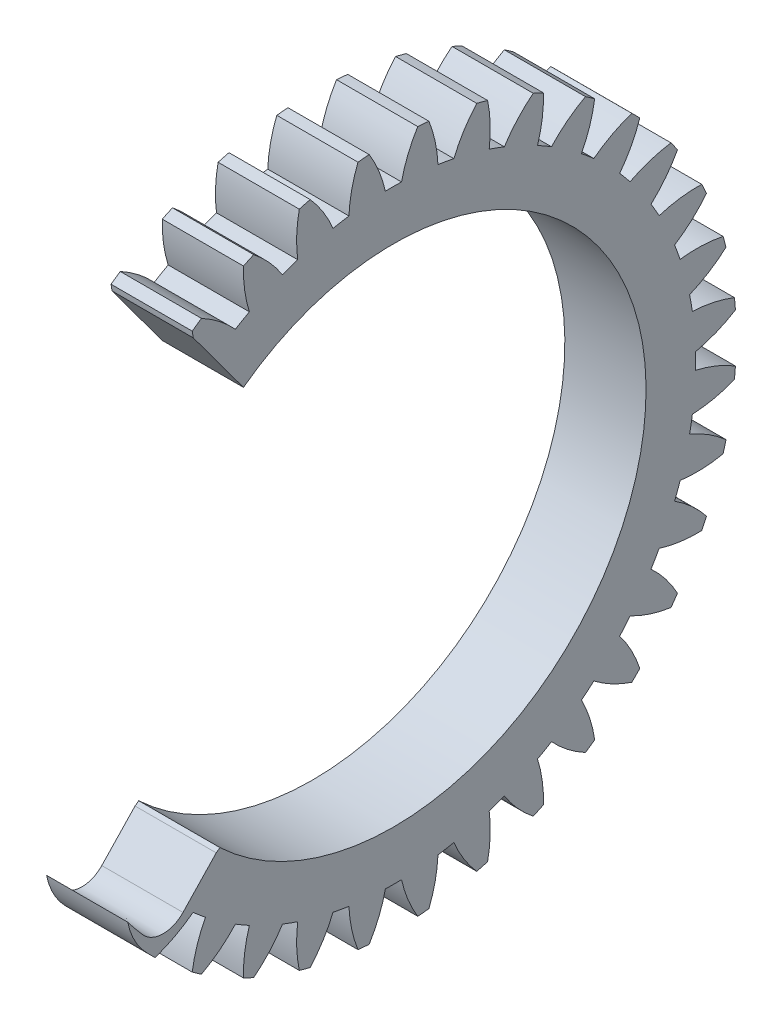
SolidWorks part; units mm, degrees
ref_plane "Plane1" through (0, 0, 0) normal (0, 0, 1) x (1, 0, 0)
ref_plane "Plane2" through (0, 0, 0) normal (0, 1, 0) x (1, 0, 0)
ref_plane "Plane3" through (0, 0, 0) normal (1, 0, 0) x (0, 0, -1)
sketch "HoldingSke" plane through (0, 0, 0) normal (0, 1, 0) x (1, 0, 0)
  line L0 (0, 0) -> (0.4045, -0.2939)
  line L1 (-15, 0) -> (100, 0) construction
  line L2 (0, 0) -> (-2.1039, 2.3779)
  line L3 (0, 0) -> (-11.863, 4.5341)
  line L4 (0, 0) -> (6.9867, 5.0761)
  line L5 (0, 0) -> (-46.8476, -17.4728)
  line L6 (0, 0) -> (-7.4607, -5.0337)
  line L7 (-2.1039, 2.3779) -> (8.6586, 51.2059)
  line L8 (-76.2, 54.61) -> (-71.9, 54.61)
  line L9 (-71.009, 38.7566) -> (-53.1078, 45.2721)
  line L10 (-76.2, 71.12) -> (104.1128, 71.12)
  line L11 (0, 0) -> (-9, 0)
  line L12 (-76.2, 101.6) -> (-76.133, 101.6)
  line L13 (24.9733, 27.94) -> (52.9518, 28.4284)
  line L14 (24.9733, 27.94) -> (24.9743, 27.94)
  line L15 (24.9733, 27.94) -> (100.4006, 29.5858)
  line L16 (-63.627, -2) -> (-12.827, -2)
  circle A0 centre (0, 0) radius 28
  circle A1 centre (0, 0) radius 33.499
  circle A2 centre (0, 0) radius 37.5
  circle A3 centre (0, 0) radius 28
  dimension "Num_teeth" = 36
  dimension "Pitch_radius" = 180.3128
  dimension "Width" = 9
  dimension "Thickness" = 9
sketch "BasProSke" plane through (0, 0, 0) normal (0, 1, 0) x (1, 0, 0)
  line L0 (-10, 0) -> (60, 0) construction
  line L1 (0, 0) -> (0, 38)
  line L2 (0, 0) -> (9, 0)
  line L3 (9, 0) -> (9, 38)
  line L4 (9, 38) -> (0, 38)
  dimension "Thickness" = 9
  dimension "Diameter" = 76
revolve "Base-Revolve" add sketch "BasProSke" angle 360 about L0
sketch "TooCutSke" plane through (0, 0, 0) normal (1, 0, 0) x (0, 0, -1)
  line L1 (0, 0) -> (0, 107) construction
  line L2 (0, 0) -> (-1.6875, 35.9604) construction
  line L3 (0, 0) -> (-6.2701, 71.6676) construction
  line L4 (-1.6875, 35.9604) -> (-3.135, 35.8338) construction
  arc A0 (0.8949, 33.487) -> (-0.8949, 33.487) centre (0, 0) ccw
  arc A1 (2.7061, 37.929) -> (-2.7061, 37.929) centre (0, 0) ccw
  circle A2 centre (0, 0) radius 36 construction
  circle A3 centre (0, 0) radius 33.8289 construction
  arc A4 (-0.8949, 33.487) -> (-2.7061, 37.929) centre (-14.9484, 30.347) ccw
  arc A5 (2.7061, 37.929) -> (0.8949, 33.487) centre (14.9484, 30.347) ccw
extrude "ToothCut" cut sketch "TooCutSke" along normal through all
fillet "Breaks" [suppressed] radius 0.04 tangent propagation no
fillet "RootFillets" [suppressed] radius 0.501
pattern_circular "TeethCuts" count 36 every 10 about axis through (-10, 0, 0) along (1, 0, 0) of "ToothCut", "RootFillets", "Breaks"
sketch "HubNeaOneSke" plane through (0, 0, 0) normal (-1, 0, 0) x (0, 0, 1)
  circle A0 centre (0, 0) radius 33.499
  dimension "Diameter" = 66.998
extrude "HubNearOne" [suppressed] add sketch "HubNeaOneSke" along normal blind 41.0001
sketch "HubNeaBotSke" plane through (0, 0, 0) normal (-1, 0, 0) x (0, 0, 1)
  circle A0 centre (0, 0) radius 33.499
  dimension "Diameter" = 66.998
extrude "HubNearBoth" [suppressed] add sketch "HubNeaBotSke" along normal blind 20.5
ref_plane "FarPln" through (9, 0, 0) normal (1, 0, 0) x (0, 0, -1)
sketch "HubFarSke" plane through (9, 0, 0) normal (1, 0, 0) x (0, 0, -1)
  circle A0 centre (0, 0) radius 33.499
  dimension "Diameter" = 66.998
extrude "HubFar" [suppressed] add sketch "HubFarSke" along normal blind 20.5
sketch "BorSke" plane through (0, 0, 0) normal (1, 0, 0) x (0, 0, -1)
  circle A0 centre (0, 0) radius 28
  dimension "Diameter" = 56
extrude "Bore" cut sketch "BorSke" along normal mid plane 100.0001
sketch "KeySke" plane through (0, 0, 0) normal (1, 0, 0) x (0, 0, -1)
  line L0 (-8, 0) -> (-8, 32.3)
  line L1 (-8, 32.3) -> (8, 32.3)
  line L2 (8, 32.3) -> (8, 0)
  line L3 (0, 0) -> (0, 34) construction
  line L4 (-8, 0) -> (8, 0)
  dimension "Width" = 16
extrude "Keyway" [suppressed] cut sketch "KeySke" along normal mid plane 100.0001
pattern_circular "Keyway2" [suppressed] count 2 every 90 about axis through (-10, 0, 0) along (1, 0, 0) reverse direction yes
sketch "Szkic1" plane through (0, 0, 0) normal (1, 0, 0) x (0, 0, -1)
  line L0 (0, 0) -> (-27.328, 37.0259)
  line L1 (-27.328, 37.0259) -> (-47.6164, -10.233)
  line L2 (-47.6164, -10.233) -> (0, 0)
extrude "Wytnij-wyciągnięcie1" cut sketch "Szkic1" along normal through all
sketch "Szkic2" plane through (0, 0, 0) normal (1, 0, 0) x (0, 0, -1)
  line L0 (-19.6433, -20.6493) -> (-23.3286, -24.5233) construction
  line L1 (-19.6433, -20.6493) -> (-23.3286, -24.5233)
  line L2 (-24.5118, 27.7159) -> (-14.2182, -16.6493)
  line L3 (-14.2182, -16.6493) -> (-19.6433, -20.6493)
  line L4 (-24.5118, 27.7159) -> (-50.9594, 25.255)
  line L5 (-50.9594, 25.255) -> (-37.7356, -29.3697)
  line L6 (-37.7356, -29.3697) -> (-27.7664, -24.4546)
  line L7 (-26.426, -27.3069) -> (-27.3069, -26.426)
  line L8 (-26.426, -27.3069) -> (-25.0675, -25.4318)
  arc A0 (-24.5118, 27.7159) -> (-27.7664, -24.4546) centre (0, 0) ccw construction
  arc A1 (-24.5118, 27.7159) -> (-27.7664, -24.4546) centre (0, 0) ccw
  arc A2 (-27.3069, -26.426) -> (-29.4473, -22.4022) centre (-21.7924, -20.9115) cw
  spline S0 degree 3 poles (393357.7903, 487398.2068) (9785.6604, 12683.3342) (-171.4024, 82.3125) (-27.1426, -24.9996) (-26.9606, -25.1074) (-26.5829, -25.2806) (-26.3868, -25.3469) (-25.9801, -25.4387) (-25.7711, -25.4633) (-25.3572, -25.469) (-25.1483, -25.4503) (-24.7384, -25.37) (-24.5404, -25.3094) (-24.158, -25.1482) (-23.9725, -25.0463) (135.3672, 85.169) (-10833.2808, 14738.6648) (-380336.4721, 497975.5957) knots -108.260231 -108.260231 -108.260231 -108.260231 0.125 0.125 0.25 0.25 0.375 0.375 0.5 0.5 0.625 0.625 0.75 0.75 0.875 0.875 117.437438 117.437438 117.437438 117.437438 only from (-27.7664, -24.4546) to (-23.3286, -24.5233) construction
  spline S1 degree 3 poles (-27.7664, -24.4546) (-27.6277, -24.6121) (-27.4749, -24.7523) (-27.1426, -24.9996) (-26.9606, -25.1074) (-26.5829, -25.2806) (-26.3868, -25.3469) (-25.9801, -25.4387) (-25.7711, -25.4633) (-25.3572, -25.469) (-25.1483, -25.4503) (-24.7384, -25.37) (-24.5404, -25.3094) (-24.158, -25.1482) (-23.9725, -25.0463) (-23.6312, -24.8102) (-23.4733, -24.6754) (-23.3286, -24.5233) knots 0 0 0 0 0.125 0.125 0.25 0.25 0.375 0.375 0.5 0.5 0.625 0.625 0.75 0.75 0.875 0.875 1 1 1 1
extrude "Wytnij-wyciągnięcie2" cut sketch "Szkic2" against normal blind 43 and the other way through all contours A1 L4 L5 L6 | A1 S1 L1 L3 L2 region at (0, -1.5762, 26.5296) region at (0, 4.8425, 39.1923)
extrude "Dodanie-wyciągnięcie1" add sketch "Szkic2<3>" along normal up to surface (9 mm away) contours A2 L6 A1 | S1 L6 A2 L7 L8 region at (0, -25.7946, 26.8655) region at (0, -23.8723, 28.649) up to face at (9, -1.2954, -9.9994)
sketch "Szkic2<3>" plane through (0, 0, 0) normal (1, 0, 0) x (0, 0, -1) same geometry as "Szkic2"
equation "' \"Module@HoldingSke\" = 6.35"
equation "' \"Num_teeth@HoldingSke\" = 12"
equation "' \"Ap@HoldingSke\" =  20"
equation "' \"Ap@HoldingSke\" = 20"
equation "' \"Width@HoldingSke\" = 0.5 * 25.4"
equation "' \"Hub_dia@HoldingSke\"= 1 * 25.4"
equation "' \"Hub_dia@HoldingSke\" = 1 * 25.4"
equation "' \"Overall_len@HoldingSke\" = 1.0 * 25.4"
equation "' \"Bore@HoldingSke\" = 0.75 * 25.4"
equation "' \"T_dim@HoldingSke\" = 0.1 * 25.4"
equation "' \"Width@KeySke\" = 0.25 * 25.4"
equation "' \"Show_teeth@HoldingSke\" = 13"
equation "' \"Backlash@HoldingSke\" = 0.009 * 25.4"
equation "' \"Addendum_fac@HoldingSke\" = 1.0"
equation "' \"Dedendum_fac@HoldingSke\" = 1.25"
equation "' \"Dedendum_add@HoldingSke\" = 0.00005 * 25.4"
equation "' \"Clearance_fac@HoldingSke\" = 0.25"
equation "\"Pitch@HoldingSke\" = 1 / \"Module@HoldingSke\""
equation "\"Overcut_dia@TooCutSke\" = (\"Num_teeth@HoldingSke\" + 2 * \"Addendum_fac@HoldingSke\") / \"Pitch@HoldingSke\" + 0.002 * 25.4"
equation "\"Pitch_dia@TooCutSke\" = \"Num_teeth@HoldingSke\" / \"Pitch@HoldingSke\""
equation "\"Base_dia@TooCutSke\" = \"Num_teeth@HoldingSke\" / \"Pitch@HoldingSke\" * cos((\"Ap@HoldingSke\"  * 3.14159265 / 180))"
equation "\"Root_dia@TooCutSke\" = (\"Num_teeth@HoldingSke\" + 2) / \"Pitch@HoldingSke\" - 2 * (\"Addendum_fac@HoldingSke\" + \"Dedendum_fac@HoldingSke\") / \"Pitch@HoldingSke\" - \"Dedendum_add@HoldingSke\" * 2"
equation "\"Half_ang@TooCutSke\" = 180 / \"Num_teeth@HoldingSke\""
equation "\"Half_CT@TooCutSke\" = \"Num_teeth@HoldingSke\" / \"Pitch@HoldingSke\" * sin((3.14159265 / 2 / \"Num_teeth@HoldingSke\")) / 2 - 7 * \"Backlash@HoldingSke\" / 4"
equation "\"Flank_rad@TooCutSke\" = \"Num_teeth@HoldingSke\" / \"Pitch@HoldingSke\" / 5"
equation "\"Radius@RootFillets\" = \"Clearance_fac@HoldingSke\" / \"Pitch@HoldingSke\" + \"Dedendum_add@HoldingSke\""
equation "\"Break_rad@Breaks\" = 0.02 / \"Pitch@HoldingSke\""
equation "\"Thickness@HoldingSke\" = \"Width@HoldingSke\""
equation "\"OAL@HoldingSke\" = \"Thickness@HoldingSke\""
equation "\"MHD@HoldingSke\" = (\"Num_teeth@HoldingSke\" + 2) / \"Pitch@HoldingSke\" - 2 * (\"Addendum_fac@HoldingSke\" + \"Dedendum_fac@HoldingSke\")  / \"Pitch@HoldingSke\" - \"Dedendum_add@HoldingSke\" * 2"
equation "\"MBD@HoldingSke\" = (\"Num_teeth@HoldingSke\" + 2) / \"Pitch@HoldingSke\" - 2 * (\"Addendum_fac@HoldingSke\" + \"Dedendum_fac@HoldingSke\")  / \"Pitch@HoldingSke\" - \"Dedendum_add@HoldingSke\" * 2 - 0.002 * 25.4"
equation "\"MHD@HoldingSke\" = ((sgn( \"MHD@HoldingSke\" - \"Hub_dia@HoldingSke\" )-1)*( \"MHD@HoldingSke\" - \"Hub_dia@HoldingSke\" ))/-2+ \"Hub_dia@HoldingSke\""
equation "\"MBD@HoldingSke\" = ((sgn( \"MBD@HoldingSke\" - \"Bore@HoldingSke\" )-1)*( \"MBD@HoldingSke\" - \"Bore@HoldingSke\" ))/-2+ \"Bore@HoldingSke\""
equation "\"OAL@HoldingSke\" = ((sgn( \"OAL@HoldingSke\" - \"Overall_len@HoldingSke\" )+1)*( \"OAL@HoldingSke\" - \"Overall_len@HoldingSke\" ))/2 + \"Overall_len@HoldingSke\" + 0.000002 * 25.4"
equation "\"Num_teeth@TeethCuts\" = int( \"Show_teeth@HoldingSke\" ) + 1"
equation "\"Num_teeth@TeethCuts\" = ((sgn( \"Num_teeth@TeethCuts\" - \"Num_teeth@HoldingSke\" )-1)*( \"Num_teeth@TeethCuts\" - \"Num_teeth@HoldingSke\" ))/-2+ \"Num_teeth@HoldingSke\""
equation "\"Num_teeth@TeethCuts\" = ((sgn( \"Num_teeth@TeethCuts\" - 2.0)+1)*( \"Num_teeth@TeethCuts\" - 2.0))/2 +2.0"
equation "\"Angle@TeethCuts\" = 360.0 / \"Num_teeth@HoldingSke\""
equation "\"Diameter@BasProSke\" = (\"Num_teeth@HoldingSke\" + 2 * \"Addendum_fac@HoldingSke\") / \"Pitch@HoldingSke\""
equation "\"Thickness@BasProSke\"  = \"Thickness@HoldingSke\""
equation "' \"Fillet_rad@BasProSke\" =  \"Thickness@HoldingSke\" * 0.05"
equation "' \"Fillet_rad@BasProSke\" = \"Thickness@HoldingSke\" * 0.05"
equation "\"MHD@HoldingSke\" = ((sgn( \"MHD@HoldingSke\" - \"Root_dia@TooCutSke\" )-1)*( \"MHD@HoldingSke\" - \"Root_dia@TooCutSke\" ))/-2+ \"Root_dia@TooCutSke\""
equation "\"Diameter@HubNeaOneSke\" = \"MHD@HoldingSke\""
equation "\"Length@HubNearOne\" = \"OAL@HoldingSke\" - \"Thickness@BasProSke\""
equation "\"Diameter@HubNeaBotSke\" = \"MHD@HoldingSke\""
equation "\"Length@HubNearBoth\" = ( \"OAL@HoldingSke\" - \"Thickness@BasProSke\" ) / 2.0"
equation "\"Thickness@FarPln\" = \"Thickness@BasProSke\""
equation "\"Diameter@HubFarSke\" = \"MHD@HoldingSke\""
equation "\"Length@HubFar\" = ( \"OAL@HoldingSke\" - \"Thickness@BasProSke\" ) / 2.0"
equation "\"Diameter@BorSke\" = \"MBD@HoldingSke\""
equation "\"D1@Bore\" = \"OAL@HoldingSke\" * 2.0"
equation "\"D1@Keyway\" = \"OAL@HoldingSke\" * 2.0"
equation "\"Offset@KeySke\" = \"T_dim@HoldingSke\" + \"MBD@HoldingSke\" / 2.0"
